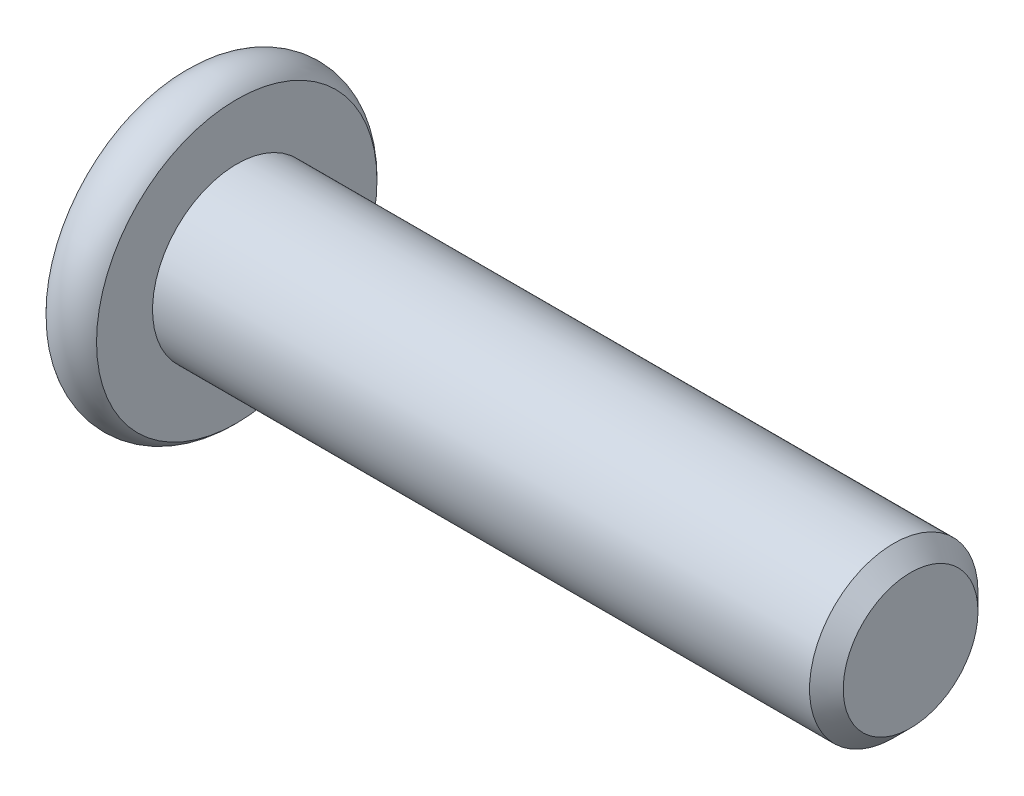
SolidWorks part; units mm, degrees
material "Alloy Steel"
ref_plane "Front Plane" through (0, 0, 0) normal (0, 0, 1) x (1, 0, 0)
ref_plane "Top Plane" through (0, 0, 0) normal (0, 1, 0) x (1, 0, 0)
ref_plane "Right Plane" through (0, 0, 0) normal (1, 0, 0) x (0, 0, -1)
other "M5 x 15"
sketch "Sketch2" plane through (0, 0, 0) normal (1, 0, 0) x (0, 0, -1)
  circle A0 centre (0, 0) radius 2.5
  dimension "D1" = 5
extrude "Boss-Extrude1" add sketch "Sketch2" against normal blind 20
chamfer "Chamfer1" distance 0.5 angle 45 1 edges at (0, 0, -2.5)
sketch "Sketch6" plane through (0, 0, 0) normal (0, 0, 1) x (1, 0, 0)
  line L0 (-21.5, 0) -> (-21.5, 4.1614)
  line L1 (-21.5, 0) -> (-20, 0)
  line L2 (-20.75, 0) -> (-20.75, 3.5) construction
  line L6 (-20, 4.1614) -> (-20, 0)
  line L8 (-20, 0) -> (-14.6471, 0) construction
  line L10 (-20, 2.5) -> (-20, -2.5) construction
  arc A0 (-21.5, 4.1614) -> (-20, 4.1614) centre (-20.75, 3.5) cw
  dimension "D3" = 1
  dimension "D1" = 1.5
  dimension "D2" = 9
revolve "Revolve1" add sketch "Sketch6" angle 360 about L8
sketch "Sketch7" plane through (-21.5, 0, 0) normal (-1, 0, 0) x (0, 0, 1)
  line L1 (0, 1.7321) -> (-1.5, 0.866)
  line L2 (-1.5, 0.866) -> (-1.5, -0.866)
  line L3 (-1.5, -0.866) -> (0, -1.7321)
  line L4 (0, -1.7321) -> (1.5, -0.866)
  line L5 (1.5, -0.866) -> (1.5, 0.866)
  line L6 (1.5, 0.866) -> (0, 1.7321)
  circle A0 centre (0, 0) radius 1.5 construction
  dimension "D1" = 3
extrude "Cut-Extrude1" cut sketch "Sketch7" against normal blind 2.3
sketch "Sketch8" plane through (-21.5, 0, 0) normal (-1, 0, 0) x (0, 0, 1)
  circle A0 centre (0, 0) radius 1.7821
  dimension "D1" = 0.05
extrude "Cut-Extrude2" cut sketch "Sketch8" against normal blind 1 draft 45
